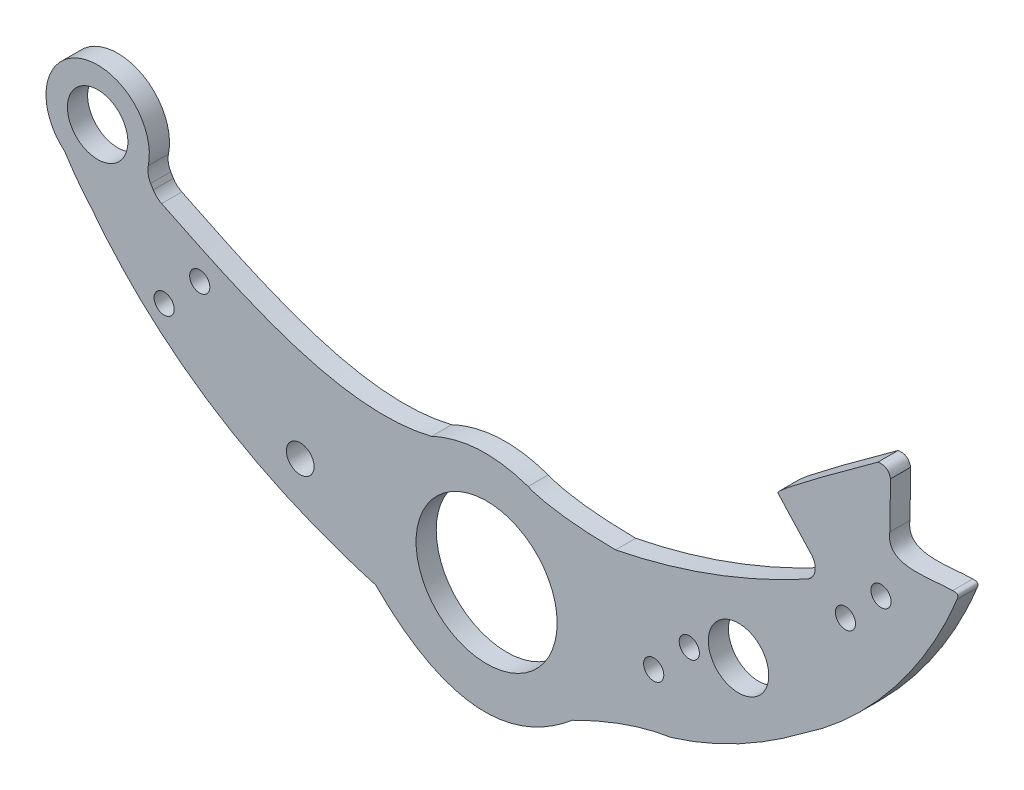
SolidWorks part; units mm, degrees
ref_plane "Ön Düzlem" through (0, 0, 0) normal (0, 0, 1) x (1, 0, 0)
ref_plane "Üst Düzlem" through (0, 0, 0) normal (0, 1, 0) x (1, 0, 0)
ref_plane "Sağ Düzlem" through (0, 0, 0) normal (1, 0, 0) x (0, 0, -1)
sketch "Model" plane through (0, 0, 0) normal (0, 0, 1) x (1, 0, 0)
  circle A0 centre (3110.9785, 2130.2209) radius 4.25
  circle A1 centre (3151.1813, 2092.8823) radius 2.7507
  circle A2 centre (3131.2383, 2113.3906) radius 2
  circle A3 centre (3124.176, 2106.0664) radius 2
  circle A4 centre (3266.4542, 2126.9365) radius 2
  circle A5 centre (3259.3919, 2119.6123) radius 2
  circle A6 centre (3228.4043, 2099.0756) radius 2
  circle A7 centre (3221.3419, 2091.7514) radius 2
  spline S0 degree 3 poles (3109.6379, 2115.3775) (3122.9132, 2098.0014) (3141.753, 2085.6566) (3166.1571, 2078.6647) knots 0 0 0 0 0.026316 0.026316 0.026316 0.026316
  spline S1 degree 3 poles (3166.1571, 2078.6647) (3179.3695, 2065.4035) (3192.3859, 2064.1655) (3205.2063, 2074.9508) knots 0.052632 0.052632 0.052632 0.052632 0.078947 0.078947 0.078947 0.078947
  spline S2 degree 3 poles (3205.2063, 2074.9508) (3212.4443, 2078.614) (3218.9967, 2080.8955) (3224.8636, 2081.7951) knots 0.105263 0.105263 0.105263 0.105263 0.131579 0.131579 0.131579 0.131579
  spline S3 degree 3 poles (3224.8636, 2081.7951) (3233.6434, 2084.4973) (3242.3977, 2089.1308) (3251.1263, 2095.6958) knots 0.157895 0.157895 0.157895 0.157895 0.184211 0.184211 0.184211 0.184211
  spline S4 degree 3 poles (3251.1263, 2095.6958) (3263.9323, 2104.2828) (3275.3481, 2118.4045) (3281.5007, 2133.8165) knots 0.210526 0.210526 0.210526 0.210526 0.236842 0.236842 0.236842 0.236842
  spline S5 degree 3 poles (3281.5007, 2133.8165) (3281.951, 2134.6871) (3281.668, 2135.0673) (3280.6517, 2134.9569) knots 0.263158 0.263158 0.263158 0.263158 0.289474 0.289474 0.289474 0.289474
  spline S6 degree 3 poles (3280.6517, 2134.9569) (3276.7237, 2135.0506) (3267.2843, 2132.5649) (3268.21, 2138.83) knots 0.315789 0.315789 0.315789 0.315789 0.342105 0.342105 0.342105 0.342105
  spline S7 degree 2 poles (3268.21, 2138.83) (3268.2982, 2144.949) (3268.3423, 2148.0086) knots 0.368421 0.368421 0.368421 0.394737 0.394737 0.394737
  spline S8 degree 3 poles (3268.3423, 2148.0086) (3268.0575, 2149.3242) (3267.2219, 2149.8636) (3265.8354, 2149.6268) knots 0.421053 0.421053 0.421053 0.421053 0.447368 0.447368 0.447368 0.447368
  spline S9 degree 3 poles (3265.8354, 2149.6268) (3252.2971, 2139.8335) (3245.6739, 2134.7666) (3245.9657, 2134.4262) knots 0.473684 0.473684 0.473684 0.473684 0.5 0.5 0.5 0.5
  spline S10 degree 2 poles (3245.9657, 2134.4262) (3252.1024, 2127.7409) (3255.1706, 2124.3982) knots 0.526316 0.526316 0.526316 0.552632 0.552632 0.552632
  spline S11 degree 3 poles (3255.1706, 2124.3982) (3241.721, 2116.6267) (3227.9176, 2111.3299) (3213.7606, 2108.5078) knots 0.578947 0.578947 0.578947 0.578947 0.605263 0.605263 0.605263 0.605263
  spline S12 degree 3 poles (3213.7606, 2108.5078) (3203.7795, 2108.569) (3198.0745, 2109.8925) (3196.4112, 2110.7361) knots 0.631579 0.631579 0.631579 0.631579 0.657895 0.657895 0.657895 0.657895
  spline S13 degree 3 poles (3196.4112, 2110.7361) (3189.8155, 2113.0117) (3183.422, 2112.6843) (3177.2308, 2109.7542) knots 0.684211 0.684211 0.684211 0.684211 0.710526 0.710526 0.710526 0.710526
  spline S14 degree 3 poles (3177.2308, 2109.7542) (3158.7924, 2105.2174) (3138.8295, 2115.6897) (3122.6364, 2123.4956) knots 0.736842 0.736842 0.736842 0.736842 0.763158 0.763158 0.763158 0.763158
  spline S15 degree 3 poles (3122.6364, 2123.4956) (3121.0569, 2125.9883) (3120.3319, 2127.4031) (3120.4612, 2127.7398) knots 0.789474 0.789474 0.789474 0.789474 0.815789 0.815789 0.815789 0.815789
  spline S16 degree 3 poles (3120.4612, 2127.7398) (3120.6529, 2134.0301) (3118.796, 2137.7617) (3114.8906, 2138.9346) knots 0.842105 0.842105 0.842105 0.842105 0.868421 0.868421 0.868421 0.868421
  spline S17 degree 3 poles (3114.8906, 2138.9346) (3107.8646, 2140.7997) (3103.2663, 2138.3238) (3101.096, 2131.5066) knots 0.894737 0.894737 0.894737 0.894737 0.921053 0.921053 0.921053 0.921053
  spline S18 degree 3 poles (3101.096, 2131.5066) (3101.3108, 2127.067) (3104.1581, 2121.6907) (3109.6379, 2115.3775) knots 0.947368 0.947368 0.947368 0.947368 1 1 1 1
  spline S19 degree 3 poles (3202.1091, 2089.9194) (3202.1091, 2097.6514) (3195.8411, 2103.9194) (3188.1091, 2103.9194) knots 0 0 0 0 0.2 0.2 0.2 0.2
  spline S20 degree 3 poles (3188.1091, 2103.9194) (3180.3771, 2103.9195) (3174.1091, 2097.6515) (3174.1091, 2089.9195) knots 0.2 0.2 0.2 0.2 0.4 0.4 0.4 0.4
  spline S21 degree 3 poles (3174.1091, 2089.9195) (3174.1091, 2082.1875) (3180.377, 2075.9195) (3188.109, 2075.9194) knots 0.4 0.4 0.4 0.4 0.6 0.6 0.6 0.6
  spline S22 degree 3 poles (3188.109, 2075.9194) (3195.841, 2075.9194) (3202.109, 2082.1874) (3202.1091, 2089.9194) knots 0.6 0.6 0.6 0.6 1 1 1 1
base flange "Taban-Flanş1" sketch "Model" thickness 4 reverse thickness direction no parameters "D1"=1.5
sketch "Çizim1" plane through (0, 0, 0) normal (0, 0, 1) x (1, 0, 0)
  line L1 (3170.8148, 2075.6068) -> (3204.0759, 2075.6068)
  line L2 (3170.8148, 2075.6068) -> (3170.8148, 2104.4597)
  line L3 (3170.8148, 2104.4597) -> (3204.0759, 2104.4597)
  line L4 (3204.0759, 2075.6068) -> (3204.0759, 2104.4597)
  line L5 (3170.8148, 2075.6068) -> (3204.0759, 2104.4597) construction
  line L6 (3170.8148, 2104.4597) -> (3204.0759, 2075.6068) construction
  point P0 (3187.4454, 2090.0332)
base flange "Sekme1" sketch "Çizim1" thickness 4 reverse thickness direction no parameters "D1"=1.5
sketch "Çizim4" plane through (0, 0, 0) normal (0, 0, 1) x (1, 0, 0)
  circle A0 centre (3188.1762, 2090.1223) radius 14
  dimension "D1" = 28
extrude "Kes-Ekstrüzyon1" cut sketch "Çizim4" against normal blind 10 normal cut yes
sketch "Çizim5" plane through (0, 0, -4) normal (0, 0, -1) x (-1, 0, 0)
  circle A0 centre (-3238.1762, 2102.1223) radius 6
  dimension "D1" = 12
  dimension "D2" = 50
  dimension "D3" = 12
extrude "Kes-Ekstrüzyon2" cut sketch "Çizim5" against normal blind 10 normal cut yes
fillet "Radyus1" radius 3 1 edges at (3255.1706, 2124.3982, -2)
sketch "Çizim6" plane through (0, 0, -4) normal (0, 0, -1) x (-1, 0, 0)
  circle A0 centre (-3110.9785, 2130.2209) radius 10.2551
  circle A1 centre (-3110.9785, 2130.2209) radius 3.7971
base flange "Sekme2" sketch "Çizim6" thickness 4 reverse thickness direction no parameters "D1"=1.5
sketch "Çizim9" plane through (0, 0, -4) normal (0, 0, -1) x (-1, 0, 0)
  circle A0 centre (-3110.9785, 2130.2209) radius 6
  dimension "D1" = 12
extrude "Kes-Ekstrüzyon3" cut sketch "Çizim9" against normal blind 10 normal cut yes
fillet "Radyus2" radius 4 2 edges at (3122.6364, 2123.4956, -2) (3120.6801, 2126.8974, -2)
sketch "Büküm-Çizgileri1" [suppressed] plane through (0, 0, 0) normal (0, 1, 0) x (1, 0, 0)
sketch "Sınırlandırma-Kutusu1" [suppressed] plane through (0, 0, 0) normal (0, 1, 0) x (1, 0, 0)
sheet metal parameters "Sac-Levha1" thickness 4 parameters "D1"=1.5
flat pattern "Düz-Çoğaltma1" [suppressed]
sketch "Büküm-Çizgileri2" plane through (0, 0, 0) normal (0, 1, 0) x (1, 0, 0)
sketch3d "Sınırlandırma-Kutusu2" [suppressed]
  line L0 (-2.2018, -61.8422, 0) -> (-182.2481, -50.1349, 0) construction
  line L1 (2.7792, 14.7604, 0) -> (-177.267, 26.4677, 0) construction
  line L2 (-2.2018, -61.8422, 0) -> (2.7792, 14.7604, 0) construction
  line L3 (-182.2481, -50.1349, 0) -> (-177.267, 26.4677, 0) construction
sheet metal parameters "Sac-Levha2" thickness 4 parameters "D1"=1.5
flat pattern "Düz-Çoğaltma2"
sketch "Büküm-Çizgileri3" plane through (0, 0, 0) normal (0, 1, 0) x (1, 0, 0)
sketch3d "Sınırlandırma-Kutusu3" [suppressed]
  line L0 (2.2018, -61.8422, 0) -> (182.2481, -50.1349, 0) construction
  line L1 (-2.7792, 14.7604, 0) -> (177.267, 26.4677, 0) construction
  line L2 (2.2018, -61.8422, 0) -> (-2.7792, 14.7604, 0) construction
  line L3 (182.2481, -50.1349, 0) -> (177.267, 26.4677, 0) construction
sheet metal parameters "Sac-Levha3" thickness 4 parameters "D1"=1.5
flat pattern "Düz-Çoğaltma2"
sketch "Büküm-Çizgileri3" plane through (0, 0, 0) normal (0, 1, 0) x (1, 0, 0)
sketch3d "Sınırlandırma-Kutusu3" [suppressed]
  line L0 (2.2018, -61.8422, 0) -> (182.2481, -50.1349, 0) construction
  line L1 (-2.7792, 14.7604, 0) -> (177.267, 26.4677, 0) construction
  line L2 (2.2018, -61.8422, 0) -> (-2.7792, 14.7604, 0) construction
  line L3 (182.2481, -50.1349, 0) -> (177.267, 26.4677, 0) construction
sheet metal parameters "Sac-Levha4" thickness 4 parameters "D1"=1.5
flat pattern "Düz-Çoğaltma2"
sketch "Büküm-Çizgileri3" plane through (0, 0, 0) normal (0, 1, 0) x (1, 0, 0)
sketch3d "Sınırlandırma-Kutusu3" [suppressed]
  line L0 (2.2018, -61.8422, 0) -> (182.2481, -50.1349, 0) construction
  line L1 (-2.7792, 14.7604, 0) -> (177.267, 26.4677, 0) construction
  line L2 (2.2018, -61.8422, 0) -> (-2.7792, 14.7604, 0) construction
  line L3 (182.2481, -50.1349, 0) -> (177.267, 26.4677, 0) construction
sheet metal parameters "Sac-Levha5" thickness 4 parameters "D1"=1.5
flat pattern "Düz-Çoğaltma5"
sketch "Büküm-Çizgileri4" plane through (0, 0, 0) normal (0, 1, 0) x (1, 0, 0)
sketch3d "Sınırlandırma-Kutusu4" [suppressed]
  line L0 (1.3032, -61.4031, 0) -> (181.9261, -50.7224, 0) construction
  line L1 (-3.2566, 15.708, 0) -> (177.3663, 26.3888, 0) construction
  line L2 (1.3032, -61.4031, 0) -> (-3.2566, 15.708, 0) construction
  line L3 (181.9261, -50.7224, 0) -> (177.3663, 26.3888, 0) construction
sheet metal parameters "Sac-Levha6" thickness 4 parameters "D1"=1.5
flat pattern "Düz-Çoğaltma5"
sketch "Büküm-Çizgileri4" plane through (0, 0, 0) normal (0, 1, 0) x (1, 0, 0)
sketch3d "Sınırlandırma-Kutusu4" [suppressed]
  line L0 (1.3032, -61.4031, 0) -> (181.9261, -50.7224, 0) construction
  line L1 (-3.2566, 15.708, 0) -> (177.3663, 26.3888, 0) construction
  line L2 (1.3032, -61.4031, 0) -> (-3.2566, 15.708, 0) construction
  line L3 (181.9261, -50.7224, 0) -> (177.3663, 26.3888, 0) construction
